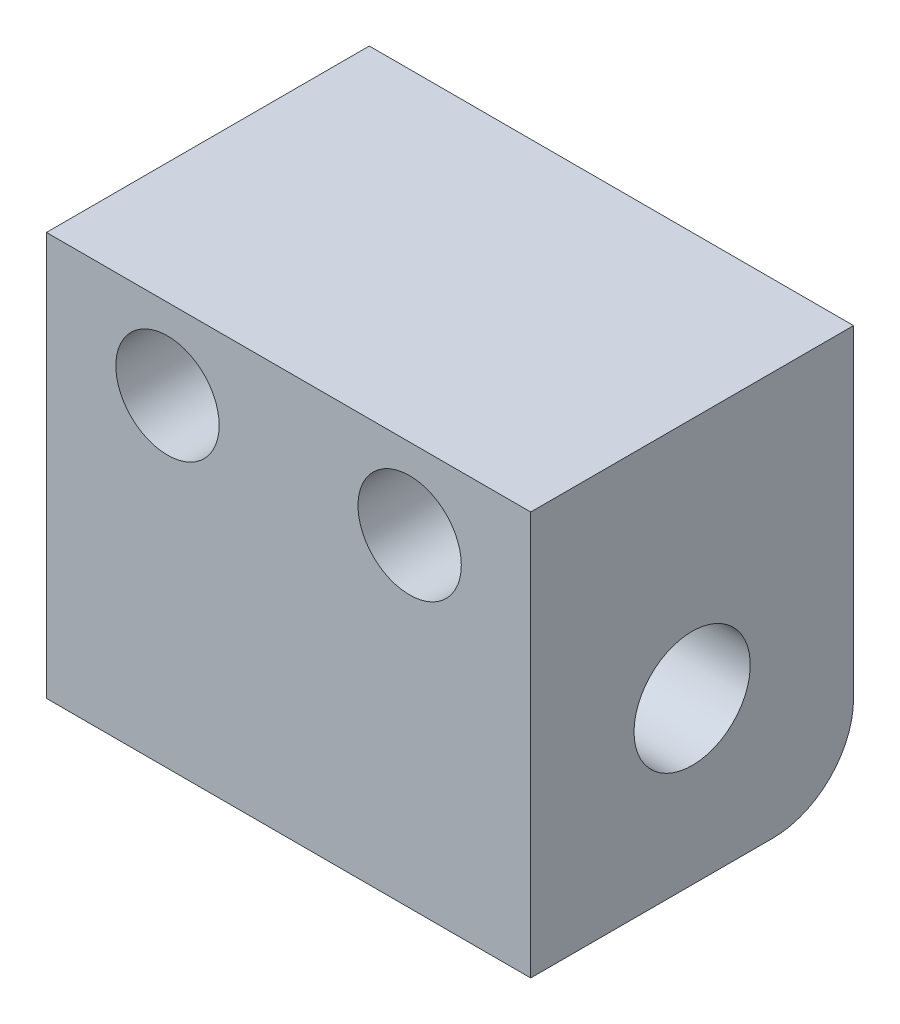
SolidWorks part; units mm, degrees
ref_plane "Front Plane" through (0, 0, 0) normal (0, 0, 1) x (1, 0, 0)
ref_plane "Top Plane" through (0, 0, 0) normal (0, 1, 0) x (1, 0, 0)
ref_plane "Right Plane" through (0, 0, 0) normal (1, 0, 0) x (0, 0, -1)
sketch "Sketch1" plane through (0, 0, 0) normal (0, 0, 1) x (1, 0, 0)
  line L0 (0, 12.7) -> (19.05, 12.7) construction
  line L1 (0, 0) -> (19.05, 0)
  line L2 (0, 0) -> (0, 15.875)
  line L3 (0, 15.875) -> (19.05, 15.875)
  line L4 (19.05, 0) -> (19.05, 15.875)
  circle A0 centre (4.7625, 12.7) radius 2.032
  circle A1 centre (14.2875, 12.7) radius 2.032
  point P14 (9.525, 15.875)
  dimension "D3" = 4.064
  dimension "D1" = 15.875
  dimension "D2" = 19.05
  dimension "D4" = 3.175
  dimension "D5" = 4.7625
  dimension "D6" = 4.7625
extrude "Boss-Extrude1" add sketch "Sketch1" along normal blind 12.7
sketch "Sketch2" plane through (0, 0, 0) normal (-1, 0, 0) x (0, 0, 1)
  line L0 (12.7, 0) -> (0, 0) construction
  circle A0 centre (6.35, 6.35) radius 2.286
  point P4 (6.35, 0)
  dimension "D2" = 4.572
  dimension "D1" = 6.35
extrude "Cut-Extrude1" cut sketch "Sketch2" against normal through all
fillet "Fillet1" radius 3.175 1 edges at (9.525, 0, 0)
